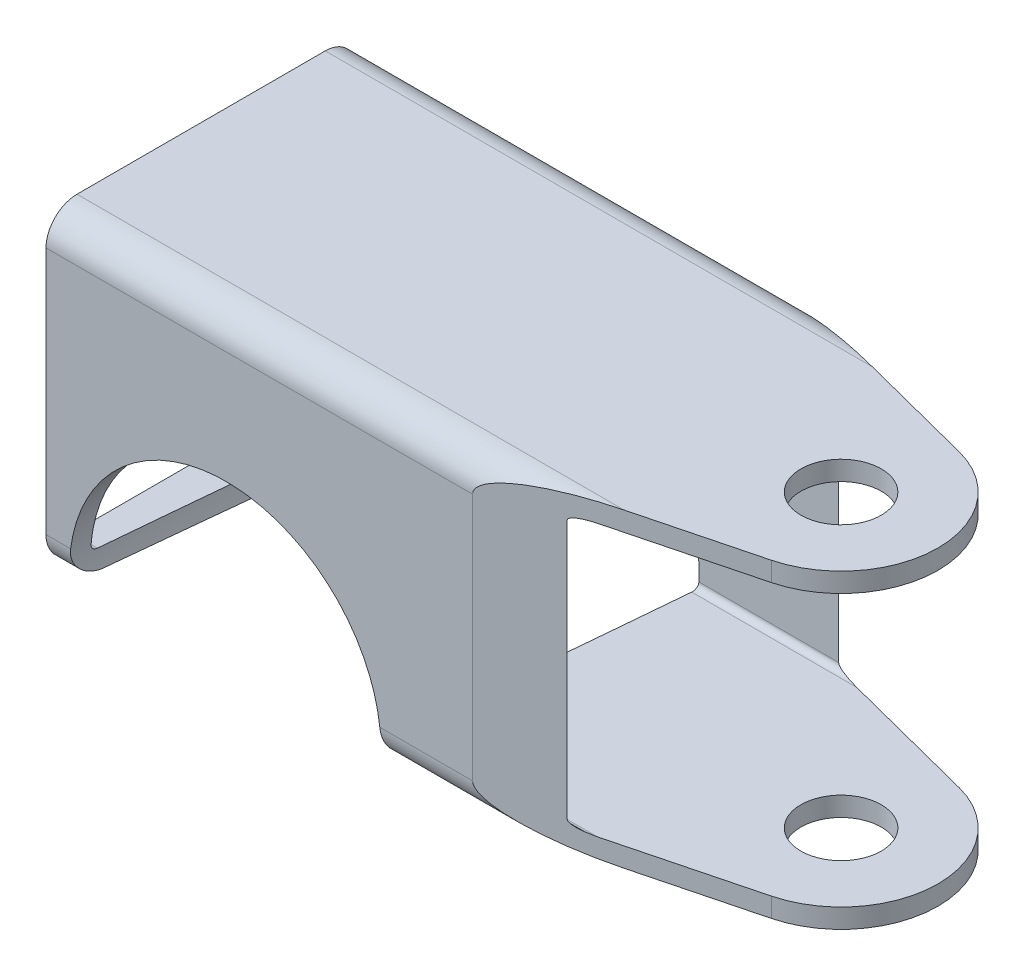
SolidWorks part; units mm, degrees
note: '?' marks a value the reader was unsure of.
ref_plane "Front Plane" through (0, 0, 0) normal (0, 0, 1) x (1, 0, 0)
ref_plane "Top Plane" through (0, 0, 0) normal (0, 1, 0) x (1, 0, 0)
ref_plane "Right Plane" through (0, 0, 0) normal (1, 0, 0) x (0, 0, -1)
sketch "Sketch1" plane through (0, 0, 0) normal (1, 0, 0) x (0, 0, -1)
  line L1 (-10.16, 12.7) -> (10.16, 12.7)
  line L2 (-12.7, 10.16) -> (-12.7, -10.16)
  line L3 (-10.16, -12.7) -> (10.16, -12.7)
  line L4 (12.7, 10.16) -> (12.7, -10.16)
  arc A0 (-10.16, 12.7) -> (-12.7, 10.16) centre (-10.16, 10.16) ccw
  arc A1 (-10.16, -12.7) -> (-12.7, -10.16) centre (-10.16, -10.16) cw
  arc A2 (10.16, 12.7) -> (12.7, 10.16) centre (10.16, 10.16) cw
  arc A3 (12.7, -10.16) -> (10.16, -12.7) centre (10.16, -10.16) cw
  point P4 (0, -12.7)
  point P7 (0, 0)
  point P15 (12.7, 0)
  dimension "D3" = 2.54
  dimension "D4" = 2.54
  dimension "D5" = 2.54
  dimension "D6" = 2.54
  dimension "D1" = 25.4
  dimension "D2" = 20.32
extrude "Boss-Extrude1" add sketch "Sketch1" along normal blind 25.4 and the other way blind 34.925
sketch "Sketch11" plane through (25.4, 0, 0) normal (1, 0, 0) x (0, 0, -1)
  line L0 (-10.16, -12.7) -> (10.16, -12.7) construction
  line L1 (-10.6045, 11.1125) -> (10.6045, 11.1125)
  line L2 (-11.1125, 10.6045) -> (-11.1125, -10.6045)
  line L3 (-10.6045, -11.1125) -> (10.6045, -11.1125)
  line L4 (11.1125, 10.6045) -> (11.1125, -10.6045)
  line L5 (10.16, 12.7) -> (-10.16, 12.7) construction
  line L6 (12.7, -10.16) -> (12.7, 10.16) construction
  line L7 (-12.7, 10.16) -> (-12.7, -10.16) construction
  arc A0 (10.6045, 11.1125) -> (11.1125, 10.6045) centre (10.6045, 10.6045) cw
  arc A1 (10.6045, -11.1125) -> (11.1125, -10.6045) centre (10.6045, -10.6045) ccw
  arc A2 (-11.1125, -10.6045) -> (-10.6045, -11.1125) centre (-10.6045, -10.6045) ccw
  arc A3 (-10.6045, 11.1125) -> (-11.1125, 10.6045) centre (-10.6045, 10.6045) ccw
  dimension "D1" = 1.5875
  dimension "D2" = 1.5875
  dimension "D3" = 1.5875
  dimension "D4" = 1.5875
  dimension "D5" = 0.508
extrude "Cut-Extrude4" cut sketch "Sketch11" against normal through all
sketch "Sketch12" plane through (0, 12.7, 0) normal (0, 1, 0) x (1, 0, 0)
  line L1 (0, 12.7) -> (50.8, 12.7)
  line L2 (50.8, 12.7) -> (50.8, -12.7)
  line L12 (50.8, -12.7) -> (0, -12.7)
  line L13 (19.4444, -7.6861) -> (0, -12.7)
  line L14 (19.4444, 7.6861) -> (0, 12.7)
  line L15 (-34.925, -12.7) -> (25.4, -12.7) construction
  line L16 (-34.925, 12.7) -> (25.4, 12.7) construction
  line L18 (25.4, 10.16) -> (25.4, -10.16) construction
  arc A1 (19.4444, -7.6861) -> (19.4444, 7.6861) centre (17.4625, 0) ccw
  point P8 (18.1688, 9.2165)
  dimension "D2" = 50.8
  dimension "D1" = 17.4625
extrude "Cut-Extrude5" cut sketch "Sketch12" against normal through all
sketch "Sketch14" plane through (0, 12.7, 0) normal (0, 1, 0) x (1, 0, 0)
  circle A0 centre (17.4625, 0) radius 3.2893
  arc A2 (19.4444, -7.6861) -> (19.4444, 7.6861) centre (17.4625, 0) ccw construction
  point P0 (17.4625, 0)
  point P6 (25.4, 0)
  dimension "D2" = 6.5786
  dimension "D1" = 7.9375
  dimension "D3" = 17.4625
extrude "Cut-Extrude6" cut sketch "Sketch14" against normal through all
ref_axis "Axis1" through (-17.1474, -9.3001, -20.4443) along (-0.0934, -0.0736, 0.9929)?
ref_point "Point2"
ref_plane "Plane1" through (-20.2649, -11.7558, 12.7) normal (-0.0934, -0.0736, 0.9929) x (0.9956, -0.0069, 0.0931)
sketch "Sketch15" plane through (-20.2649, -11.7558, 12.7) normal (-0.0934, -0.0736, 0.9929) x (0.9956, -0.0069, 0.0931)
  circle A0 centre (0, 0) radius 12.7
  dimension "D1" = 25.4
extrude "Cut-Extrude7" cut sketch "Sketch15" against normal blind 38.1 and the other way blind 12.7
